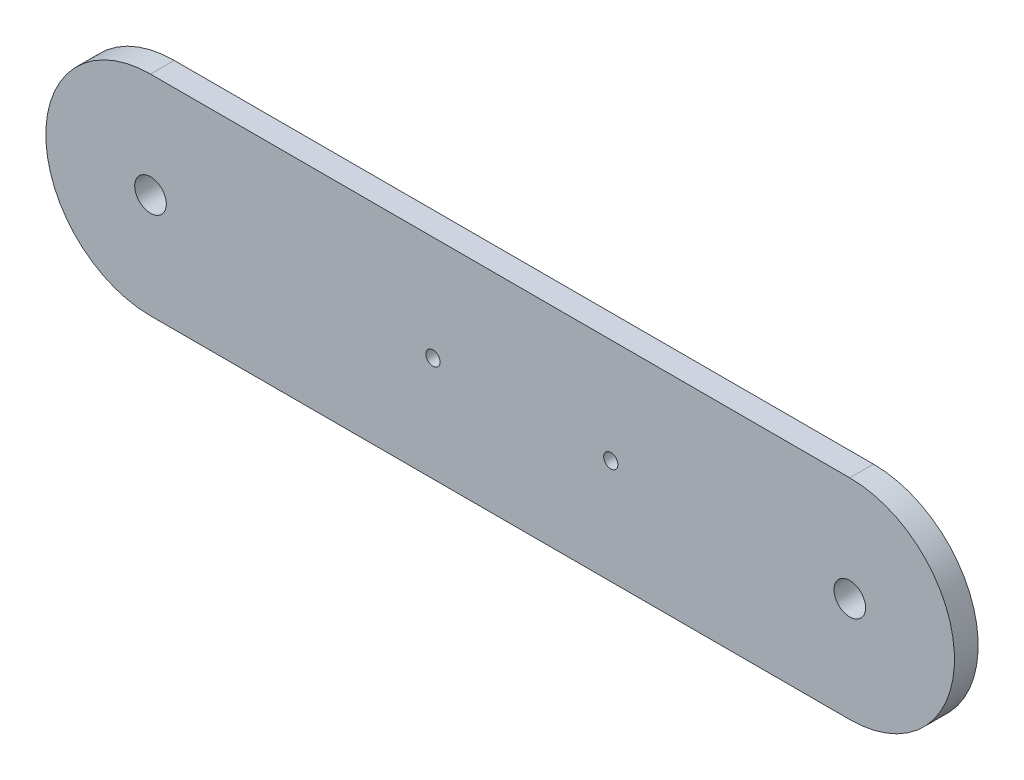
SolidWorks part; units mm, degrees
material "Balsa"
ref_plane "Plano frontal" through (0, 0, 0) normal (0, 0, 1) x (1, 0, 0)
ref_plane "Plano superior" through (0, 0, 0) normal (0, 1, 0) x (1, 0, 0)
ref_plane "Plano direito" through (0, 0, 0) normal (1, 0, 0) x (0, 0, -1)
sketch "Esboço1" plane through (0, 0, 0) normal (0, 0, 1) x (1, 0, 0)
  line L0 (-94, 26.5) -> (83, 26.5)
  line L1 (-94, -26.5) -> (83, -26.5)
  line L2 (-94, 0) -> (-20.7, 0) construction
  line L3 (-22.5, 0) -> (22.5, 0) construction
  line L5 (20.7, 0) -> (22.5, 0) construction
  arc A0 (83, -26.5) -> (83, 26.5) centre (83, 0) ccw
  arc A1 (-94, 26.5) -> (-94, -26.5) centre (-94, 0) ccw
  circle A2 centre (-94, 0) radius 4
  circle A3 centre (83, 0) radius 4
  circle A4 centre (-22.5, 0) radius 1.8
  circle A5 centre (22.5, 0) radius 1.8
  point P19 (0, 0)
  dimension "D1" = 3.6
  dimension "D5" = 8
  dimension "D6" = 26.5
  dimension "D2" = 45
  dimension "D3" = 83
  dimension "D4" = 94
extrude "Ressalto-extrusão1" add sketch "Esboço1" along normal blind 6
